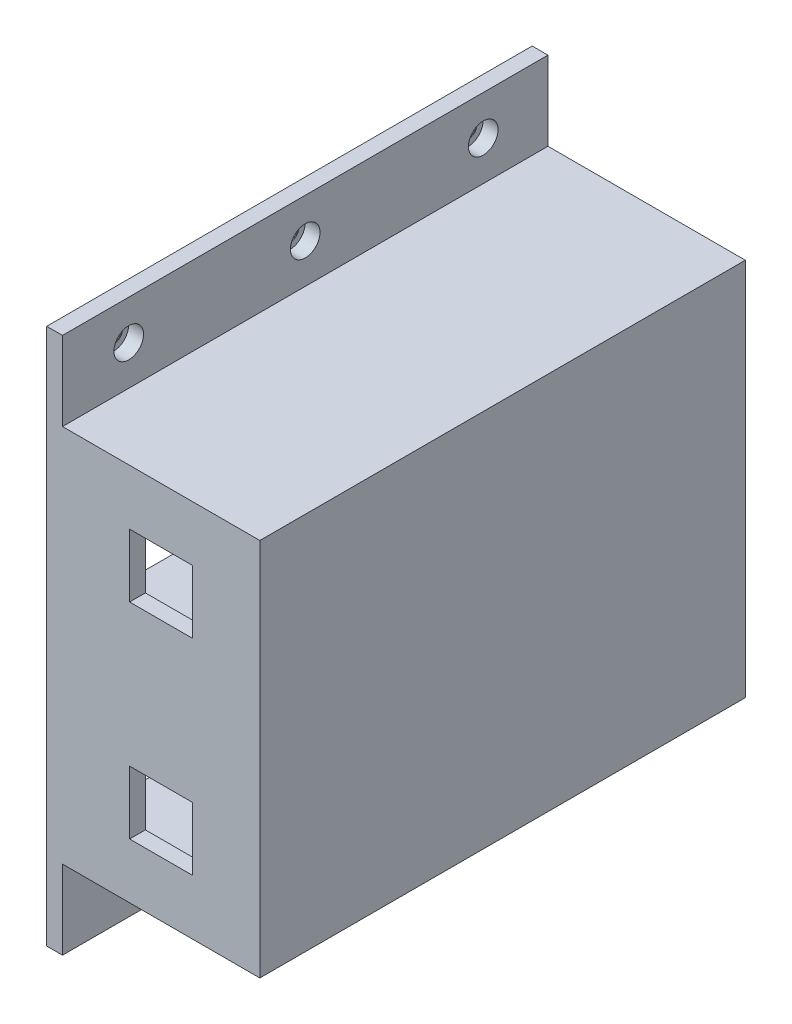
SolidWorks part; units mm, degrees
ref_plane "Front Plane" through (0, 0, 0) normal (0, 0, 1) x (1, 0, 0)
ref_plane "Top Plane" through (0, 0, 0) normal (0, 1, 0) x (1, 0, 0)
ref_plane "Right Plane" through (0, 0, 0) normal (1, 0, 0) x (0, 0, -1)
sketch "Sketch1" plane through (0, 0, 0) normal (1, 0, 0) x (0, 0, -1)
  line L0 (0, 2.54) -> (0, -2.54) construction
  line L1 (-78.105, 86.36) -> (78.105, 86.36)
  line L2 (-78.105, 86.36) -> (-78.105, -86.36)
  line L3 (-78.105, -86.36) -> (78.105, -86.36)
  line L4 (78.105, 86.36) -> (78.105, -86.36)
  line L5 (-78.105, 86.36) -> (78.105, -86.36) construction
  line L6 (-78.105, -86.36) -> (78.105, 86.36) construction
  line L7 (-73.025, 55.88) -> (73.025, 55.88)
  line L8 (-73.025, 55.88) -> (-73.025, 2.54)
  line L9 (-73.025, 2.54) -> (73.025, 2.54)
  line L10 (73.025, 55.88) -> (73.025, 2.54)
  line L11 (-73.025, 55.88) -> (73.025, 2.54) construction
  line L12 (-73.025, 2.54) -> (73.025, 55.88) construction
  line L13 (-73.025, -2.54) -> (73.025, -2.54)
  line L14 (-73.025, -2.54) -> (-73.025, -55.88)
  line L15 (-73.025, -55.88) -> (73.025, -55.88)
  line L16 (73.025, -2.54) -> (73.025, -55.88)
  line L17 (-73.025, -2.54) -> (73.025, -55.88) construction
  line L18 (-73.025, -55.88) -> (73.025, -2.54) construction
  line L19 (-78.105, 60.96) -> (78.105, 60.96)
  line L20 (-78.105, -60.96) -> (78.105, -60.96)
  point P0 (0, 0)
  point P6 (0, 29.21)
  point P11 (0, -29.21)
  point P20 (0, 0)
  dimension "D1" = 146.05
  dimension "D2" = 53.34
  dimension "D3" = 5.08
  dimension "D4" = 5.08
  dimension "D5" = 5.08
  dimension "D6" = 5.08
  dimension "D7" = 25.4
extrude "Boss-Extrude1" add sketch "Sketch1" along normal blind 5.08 contours L2 L19 L4 L1 | L20 L2 L3 L4 region at (0, 73.66, 0) region at (0, -73.66, 0)
extrude "Boss-Extrude2" add sketch "Sketch1<3>" along normal blind 63.5 contours L2 L20 L4 L19 L7 L10 L9 L8 L13 L16 L15 L14 region at (0, 0, 0)
sketch "Sketch1<3>" plane through (0, 0, 0) normal (1, 0, 0) x (0, 0, -1) same geometry as "Sketch1"
sketch "Sketch2" plane through (63.5, 0, 0) normal (1, 0, 0) x (0, 0, -1)
  line L1 (-78.105, 60.96) -> (78.105, 60.96)
  line L2 (-78.105, 60.96) -> (-78.105, -60.96)
  line L3 (-78.105, -60.96) -> (78.105, -60.96)
  line L4 (78.105, 60.96) -> (78.105, -60.96)
extrude "Boss-Extrude3" add sketch "Sketch2" along normal blind 5.08
sketch "Sketch3" plane through (0, 0, 78.105) normal (0, 0, 1) x (1, 0, 0)
  line L0 (36.83, 33.02) -> (36.83, -33.02) construction
  line L1 (26.67, 43.18) -> (46.99, 43.18)
  line L2 (26.67, 43.18) -> (26.67, 22.86)
  line L3 (26.67, 22.86) -> (46.99, 22.86)
  line L4 (46.99, 43.18) -> (46.99, 22.86)
  line L5 (26.67, 43.18) -> (46.99, 22.86) construction
  line L6 (26.67, 22.86) -> (46.99, 43.18) construction
  line L7 (26.67, -22.86) -> (46.99, -22.86)
  line L8 (26.67, -22.86) -> (26.67, -43.18)
  line L9 (26.67, -43.18) -> (46.99, -43.18)
  line L10 (46.99, -22.86) -> (46.99, -43.18)
  line L11 (26.67, -22.86) -> (46.99, -43.18) construction
  line L12 (26.67, -43.18) -> (46.99, -22.86) construction
  line L13 (68.58, 60.96) -> (5.08, 60.96) construction
  point P0 (36.83, 33.02)
  point P5 (36.83, -33.02)
  point P12 (36.83, 0)
  point P16 (36.83, 60.96)
  dimension "D1" = 20.32
  dimension "D2" = 20.32
  dimension "D3" = 45.72
extrude "Cut-Extrude1" cut sketch "Sketch3" against normal blind 5.08
sketch "Sketch4" plane through (5.08, 0, 0) normal (1, 0, 0) x (0, 0, -1)
  line L0 (-78.105, 73.66) -> (78.105, 73.66) construction
  line L1 (-78.105, 86.36) -> (-78.105, 60.96) construction
  line L2 (78.105, 86.36) -> (78.105, 60.96) construction
sketch "Sketch5" plane through (5.08, 0, 0) normal (1, 0, 0) x (0, 0, -1)
  line L0 (-78.105, -73.66) -> (78.105, -73.66) construction
  line L1 (-78.105, -60.96) -> (-78.105, -86.36) construction
  line L2 (78.105, -60.96) -> (78.105, -86.36) construction
hole_wizard "CBORE for #10 Socket Head Cap Screw1" positions "Sketch6" profile "Sketch7" counterbore size "#10" standard "ANSI Inch" end condition through all
sketch "Sketch6" plane through (5.08, 0, 0) normal (1, 0, 0) x (0, 0, -1)
  line L0 (-78.105, 73.66) -> (78.105, 73.66) construction
  point P0 (0, 73.66)
  point P4 (-56.7834, 73.66)
  point P6 (57.2848, 73.66)
sketch "Sketch7" plane through (5.08, 73.66, 0) normal (0, 1, 0) x (0, 0, -1)
  line L0 (0, 0) -> (0, 5.08)
  line L1 (0, 5.08) -> (2.8067, 5.08)
  line L3 (2.8067, 5.08) -> (2.8067, 4.826)
  line L4 (2.8067, 4.826) -> (4.7625, 4.826)
  line L5 (4.7625, 4.826) -> (4.7625, 0)
  line L7 (4.7625, 0) -> (0, 0)
  line L11 (0, -6.35) -> (0, 107.95) construction
  dimension "Thru Hole Dia." = 5.6134
  dimension "Thru Hole Depth" = 5.08
  dimension "C'Bore Dia." = 9.525
  dimension "C'Bore Depth" = 4.826
hole_wizard "CBORE for #10 Socket Head Cap Screw2" positions "Sketch8" profile "Sketch9" counterbore size "#10" standard "ANSI Inch" end condition through all
sketch "Sketch8" plane through (5.08, 0, 0) normal (1, 0, 0) x (0, 0, -1)
  line L0 (-78.105, -73.66) -> (78.105, -73.66) construction
  point P0 (0, -73.66)
  point P4 (-57.5355, -73.66)
  point P6 (59.5411, -73.66)
sketch "Sketch9" plane through (5.08, -73.66, 0) normal (0, 1, 0) x (0, 0, -1)
  line L0 (0, 0) -> (0, 5.08)
  line L1 (0, 5.08) -> (2.8067, 5.08)
  line L3 (2.8067, 5.08) -> (2.8067, 4.826)
  line L4 (2.8067, 4.826) -> (4.7625, 4.826)
  line L5 (4.7625, 4.826) -> (4.7625, 0)
  line L7 (4.7625, 0) -> (0, 0)
  line L11 (0, -6.35) -> (0, 107.95) construction
  dimension "Thru Hole Dia." = 5.6134
  dimension "Thru Hole Depth" = 5.08
  dimension "C'Bore Dia." = 9.525
  dimension "C'Bore Depth" = 4.826
